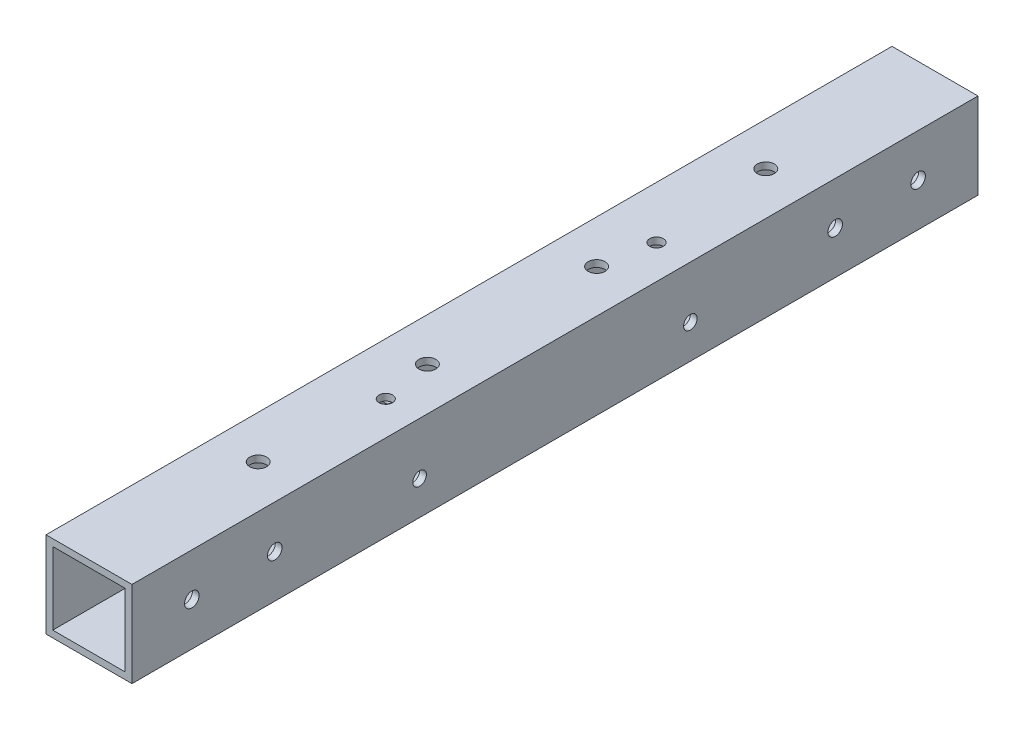
SolidWorks part; units mm, degrees
ref_plane "前基準面" through (0, 0, 0) normal (0, 0, 1) x (1, 0, 0)
ref_plane "上基準面" through (0, 0, 0) normal (0, 1, 0) x (1, 0, 0)
ref_plane "右基準面" through (0, 0, 0) normal (1, 0, 0) x (0, 0, -1)
sketch "草圖1" plane through (0, 0, 0) normal (0, 0, 1) x (1, 0, 0)
  line L0 (-10.7, 10.7) -> (10.7, 10.7)
  line L1 (-12.7, 12.7) -> (12.7, 12.7)
  line L2 (-12.7, 12.7) -> (-12.7, -12.7)
  line L3 (-12.7, -12.7) -> (12.7, -12.7)
  line L4 (12.7, 12.7) -> (12.7, -12.7)
  line L5 (-12.7, 12.7) -> (12.7, -12.7) construction
  line L6 (-12.7, -12.7) -> (12.7, 12.7) construction
  line L7 (10.7, 10.7) -> (10.7, -10.7)
  line L8 (-10.7, -10.7) -> (10.7, -10.7)
  line L9 (-10.7, 10.7) -> (-10.7, -10.7)
  point P0 (0, 0)
  dimension "D1" = 25.4
  dimension "D2" = 25.4
  dimension "D3" = 2
extrude "填料-伸長1" add sketch "草圖1" along normal blind 250 contours L1 L4 L3 L2
extrude "除料-伸長1" cut sketch "草圖1<3>" along normal through all contours L0 L7 L8 L9
sketch "草圖1<3>" plane through (0, 0, 0) normal (0, 0, 1) x (1, 0, 0) same geometry as "草圖1"
sketch "草圖2" plane through (12.7, 0, 0) normal (1, 0, 0) x (0, 0, -1)
  circle A0 centre (-232.3, 0) radius 2.15
  circle A1 centre (-207.8, 0) radius 2.15
extrude "除料-伸長2" cut sketch "草圖2" against normal blind 3
sketch "草圖3" plane through (0, -12.7, 0) normal (0, -1, 0) x (1, 0, 0)
  circle A0 centre (0, 232.3) radius 2.15
  circle A1 centre (0, 207.8) radius 2.15
extrude "除料-伸長3" cut sketch "草圖3" against normal blind 3
sketch "草圖4" plane through (12.7, 0, 0) normal (1, 0, 0) x (0, 0, -1)
  circle A0 centre (-42.2, 0) radius 2.15
  circle A1 centre (-17.7, 0) radius 2.15
extrude "除料-伸長4" cut sketch "草圖4" against normal blind 3
sketch "草圖5" plane through (0, -12.7, 0) normal (0, -1, 0) x (1, 0, 0)
  circle A0 centre (0, 42.2) radius 2.15
  circle A1 centre (0, 17.7) radius 2.15
extrude "除料-伸長5" cut sketch "草圖5" against normal blind 3
sketch "草圖6" plane through (-12.7, 0, 0) normal (-1, 0, 0) x (0, 0, 1)
  line L0 (0, 0) -> (50, 0) construction
  line L1 (0, 12.7) -> (0, -12.7) construction
  line L2 (50, 0) -> (100, 0) construction
  line L3 (100, 0) -> (150, 0) construction
  line L4 (150, 0) -> (200, 0) construction
  circle A0 centre (100, 0) radius 2.5
  circle A1 centre (150, 0) radius 2.5
  circle A2 centre (200, 0) radius 2.5
  circle A3 centre (50, 0) radius 2.5
  dimension "D5" = 5
  dimension "D6" = 5
  dimension "D7" = 5
  dimension "D8" = 5
  dimension "D1" = 50
  dimension "D2" = 50
  dimension "D3" = 50
  dimension "D4" = 50
extrude "除料-伸長6" cut sketch "草圖6" against normal blind 10
sketch "草圖7" plane through (0, 12.7, 0) normal (0, 1, 0) x (1, 0, 0)
  line L0 (0, 0) -> (0, -50) construction
  line L1 (-12.7, 0) -> (12.7, 0) construction
  line L2 (0, -50) -> (0, -100) construction
  line L3 (0, -100) -> (0, -150) construction
  line L4 (0, -150) -> (0, -200) construction
  circle A0 centre (0, -50) radius 2.5
  circle A1 centre (0, -100) radius 2.5
  circle A2 centre (0, -150) radius 2.5
  circle A3 centre (0, -200) radius 2.5
  dimension "D5" = 5
  dimension "D6" = 5
  dimension "D7" = 5
  dimension "D8" = 5
  dimension "D1" = 50
  dimension "D2" = 50
  dimension "D3" = 50
  dimension "D4" = 50
extrude "除料-伸長7" cut sketch "草圖7" against normal blind 10
sketch "草圖9" plane through (0, -12.7, 0) normal (0, -1, 0) x (1, 0, 0)
  circle A0 centre (2.7, 165) radius 2
  circle A1 centre (2.7, 85) radius 2
extrude "除料-伸長8" cut sketch "草圖9" against normal blind 25.4
sketch "草圖10" plane through (12.7, 0, 0) normal (1, 0, 0) x (0, 0, -1)
  circle A0 centre (-85, -2.7) radius 2
  circle A1 centre (-165, -2.7) radius 2
extrude "除料-伸長9" cut sketch "草圖10" against normal blind 25.4
